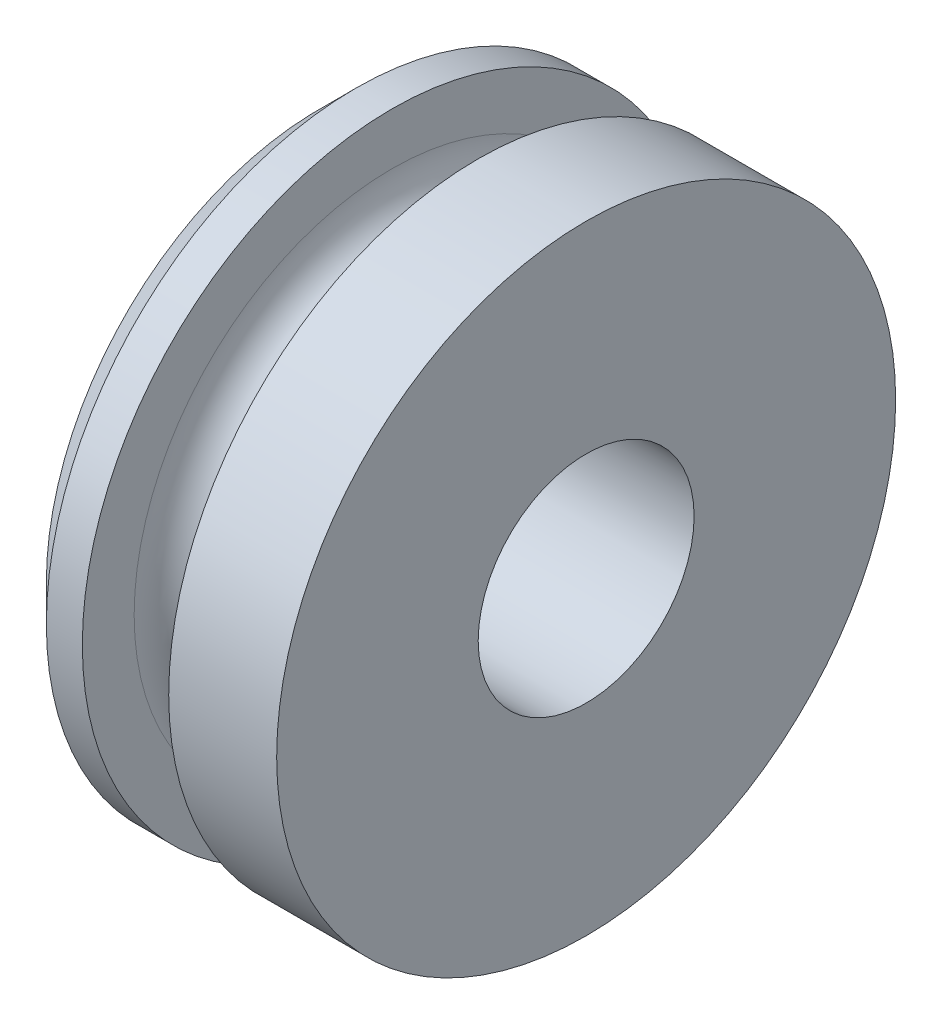
SolidWorks part; units mm, degrees
material "6061-T6 (SS)"
ref_plane "Front Plane" through (0, 0, 0) normal (0, 0, 1) x (1, 0, 0)
ref_plane "Top Plane" through (0, 0, 0) normal (0, 1, 0) x (1, 0, 0)
ref_plane "Right Plane" through (0, 0, 0) normal (1, 0, 0) x (0, 0, -1)
sketch "Sketch1" plane through (0, 0, 0) normal (0, 0, 1) x (1, 0, 0)
  line L0 (0, 9.525) -> (23.495, 9.525)
  line L1 (0, 0) -> (23.495, 0) construction
  line L2 (0, 0) -> (0, 27.305)
  line L3 (0, 27.305) -> (6.35, 27.305)
  line L4 (6.35, 22.733) -> (6.35, 27.305)
  line L6 (13.97, 22.733) -> (13.97, 27.305)
  line L7 (13.97, 27.305) -> (23.495, 27.305)
  line L8 (23.495, 0) -> (23.495, 27.305)
  arc A0 (6.35, 22.733) -> (13.97, 22.733) centre (10.16, 22.733) ccw
  dimension "D1" = 3.81
  dimension "D2" = 6.35
  dimension "D3" = 27.305
  dimension "D4" = 4.572
  dimension "D5" = 9.525
  dimension "D6" = 9.525
revolve "Revolve1" add sketch "Sketch1" angle 360 about L1 region at (12.0016, 17.6051, 0)
chamfer "Chamfer1" distance 3.175 angle 45 1 edges at (0, 0, 27.305)
